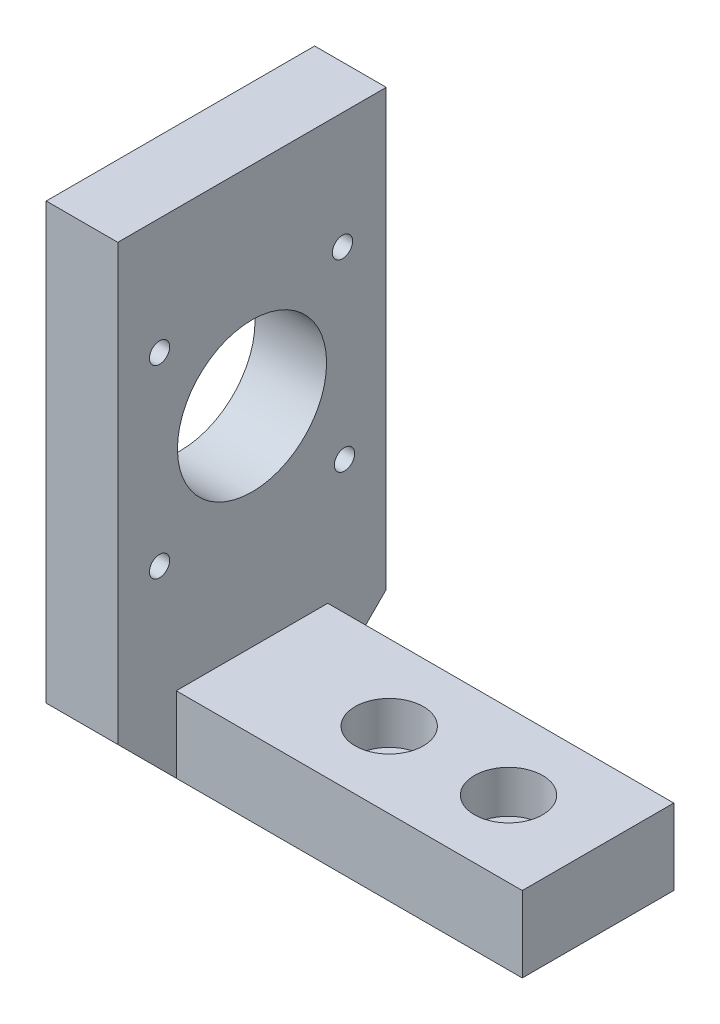
SolidWorks part; units mm, degrees
ref_plane "Front Plane" through (0, 0, 0) normal (0, 0, 1) x (1, 0, 0)
ref_plane "Top Plane" through (0, 0, 0) normal (0, 1, 0) x (1, 0, 0)
ref_plane "Right Plane" through (0, 0, 0) normal (1, 0, 0) x (0, 0, -1)
sketch "Sketch1" plane through (0, 0, 0) normal (0, 1, 0) x (1, 0, 0)
  line L1 (-35, -12.7) -> (35, -12.7)
  line L2 (-35, -12.7) -> (-35, 12.7)
  line L3 (-35, 12.7) -> (35, 12.7)
  line L4 (35, -12.7) -> (35, 12.7)
  line L5 (-35, -12.7) -> (35, 12.7) construction
  line L6 (-35, 12.7) -> (35, -12.7) construction
  point P0 (0, 0)
  dimension "D1" = 25.4
  dimension "D2" = 70
extrude "Boss-Extrude1" add sketch "Sketch1" along normal blind 12.7
sketch "Sketch2" plane through (-35, 0, 0) normal (-1, 0, 0) x (0, 0, 1)
  line L1 (-15.5, 32.2) -> (15.5, 32.2) construction
  line L2 (-15.5, 32.2) -> (-15.5, 63.2) construction
  line L3 (-15.5, 63.2) -> (15.5, 63.2) construction
  line L4 (15.5, 32.2) -> (15.5, 63.2) construction
  line L5 (-15.5, 32.2) -> (15.5, 63.2) construction
  line L6 (-15.5, 63.2) -> (15.5, 32.2) construction
  line L7 (-12.7, 12.7) -> (12.7, 12.7) construction
  line L8 (-22.5, 12.7) -> (22.5, 12.7)
  line L9 (-22.5, 12.7) -> (-22.5, 82.7)
  line L10 (-22.5, 82.7) -> (22.5, 82.7)
  line L11 (22.5, 12.7) -> (22.5, 82.7)
  line L12 (-22.5, 12.7) -> (22.5, 82.7) construction
  line L13 (-22.5, 82.7) -> (22.5, 12.7) construction
  circle A0 centre (0, 47.7) radius 12.5
  point P0 (0, 47.7)
  point P5 (0, 47.7)
  dimension "D3" = 25
  dimension "D1" = 31
  dimension "D2" = 70
  dimension "D4" = 45
extrude "Boss-Extrude2" add sketch "Sketch2" against normal blind 12
chamfer "Chamfer1" distance 12.7 angle 45 2 edges at (-29, 12.7, 12.7) (-29, 12.7, -12.7)
hole_wizard "M3 Clearance Hole1" positions "Sketch3" profile "Sketch4" hole size "M3" standard "ANSI Metric" end condition through all
sketch "Sketch3" plane through (-35, 0, 0) normal (-1, 0, 0) x (0, 0, 1)
  line L0 (-15.5, 63.2) -> (15.5, 63.2) construction
  point P0 (-15.1608, 63.2)
  point P4 (15.5, 63.2)
  point P7 (15.5, 32.2)
  point P10 (-15.5, 32.2)
sketch "Sketch4" plane through (-35, 63.2, -15.1608) normal (0, 1, 0) x (0, 0, 1)
  line L0 (0, 0) -> (0, 70)
  line L1 (0, 70) -> (1.7, 70)
  line L2 (1.7, 70) -> (1.7, 0)
  line L5 (1.7, 0) -> (0, 0)
  line L11 (0, -6.35) -> (0, 107.95) construction
  dimension "Thru Hole Dia." = 3.4
  dimension "Thru Hole Depth" = 70
sketch "Sketch5" plane through (0, 12.7, 0) normal (0, 1, 0) x (1, 0, 0)
  line L0 (35, 0) -> (-23, 0) construction
  line L1 (35, -12.7) -> (35, 12.7) construction
  line L2 (-23, -22.5) -> (-23, 22.5) construction
  point P6 (20, 0)
  point P8 (0, 0)
  dimension "D1" = 15
  dimension "D2" = 20
hole_wizard "1/4 Clearance Hole1" positions "Sketch6" profile "Sketch7" hole size "1/4" standard "ANSI Inch" end condition through all
sketch "Sketch6" plane through (0, 12.7, 0) normal (0, 1, 0) x (1, 0, 0)
  point P3 (20, 0)
  point P7 (0, 0)
sketch "Sketch7" plane through (20, 12.7, 0) normal (1, 0, 0) x (0, 0, 1)
  line L0 (0, 0) -> (0, 12.7)
  line L1 (0, 12.7) -> (3.3782, 12.7)
  line L2 (3.3782, 12.7) -> (3.3782, 0)
  line L5 (3.3782, 0) -> (0, 0)
  line L11 (0, -6.35) -> (0, 107.95) construction
  dimension "Thru Hole Dia." = 6.7564
  dimension "Thru Hole Depth" = 12.7
sketch "Sketch8" plane through (0, 12.7, 0) normal (0, 1, 0) x (1, 0, 0)
  circle A1 centre (20, 0) radius 5.715
  circle A2 centre (0, 0) radius 5.715
  dimension "D1" = 11.43
extrude "Cut-Extrude1" cut sketch "Sketch8" against normal blind 7.112
